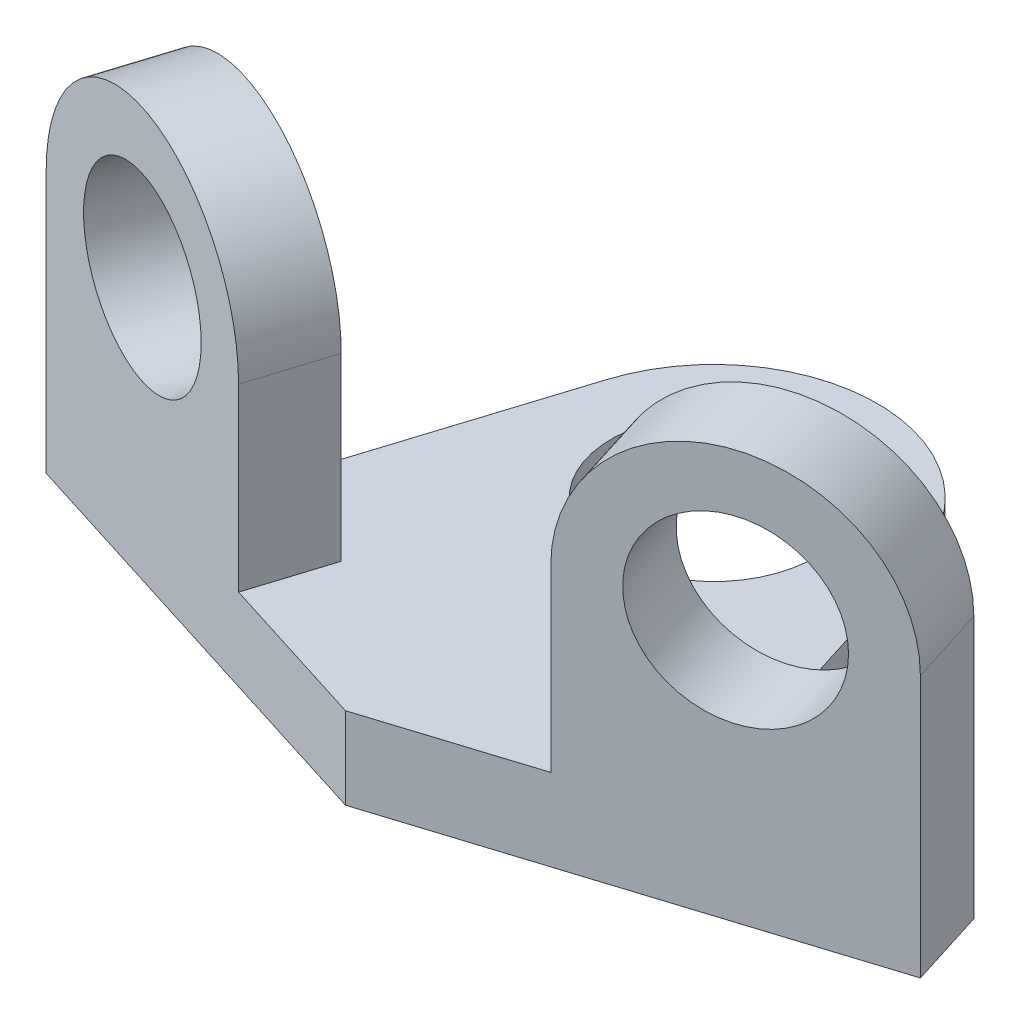
SolidWorks part; units mm, degrees
ref_plane "Front Plane" through (0, 0, 0) normal (0, 0, 1) x (1, 0, 0)
ref_plane "Top Plane" through (0, 0, 0) normal (0, 1, 0) x (1, 0, 0)
ref_plane "Right Plane" through (0, 0, 0) normal (1, 0, 0) x (0, 0, -1)
sketch "Sketch1" plane through (0, 0, 0) normal (0, 1, 0) x (1, 0, 0)
  line L0 (-19.0743, 6.0141) -> (-31.9798, -34.9168)
  line L1 (19.0743, 6.0141) -> (31.9798, -34.9168)
  line L2 (0, 0) -> (0, -45)
  line L3 (0, -45) -> (31.9798, -34.9168)
  line L4 (31.9798, -34.9168) -> (0, -45)
  line L5 (0, -45) -> (-31.9798, -34.9168)
  line L6 (-19.0743, -38.9859) -> (-16.0673, -29.4487)
  line L7 (-16.0673, -29.4487) -> (-50.4011, -18.6233)
  line L8 (-50.4011, -18.6233) -> (-53.4081, -28.1605)
  line L9 (-53.4081, -28.1605) -> (-31.9798, -34.9168)
  line L10 (19.0743, -38.9859) -> (16.0673, -29.4487)
  line L11 (16.0673, -29.4487) -> (50.4011, -18.6233)
  line L12 (50.4011, -18.6233) -> (53.4081, -28.1605)
  line L13 (53.4081, -28.1605) -> (31.9798, -34.9168)
  circle A0 centre (0, 0) radius 12.5
  circle A1 centre (0, 0) radius 20
  dimension "D1" = 25
  dimension "D2" = 40
  dimension "D3" = 45
  dimension "D4" = 17.5
  dimension "D5" = 17.5
  dimension "D6" = 20
  dimension "D7" = 20
  dimension "D8" = 10
  dimension "D9" = 10
  dimension "D10" = 36
  dimension "D11" = 36
extrude "Boss-Extrude1" add sketch "Sketch1" along normal blind 10 contours A1 A0 | A1 L0 L7 L6 L5 L2 | A1 L2 L3 L10 L11 L1 region at (-12.9352, 0, 25.7062) region at (0, 0, -19.4343) region at (12.9352, 0, 25.7062)
extrude "Boss-Extrude2" add sketch "Sketch1<3>" along normal blind 32 contours L8 L9 L0 L7 | L6 L7 L0 L5 | L11 L10 L4 L1 | L13 L12 L11 L1 region at (-24.0235, 0, 32.1828) region at (-41.1905, 0, 26.7701) region at (41.1905, 0, 26.7701) region at (24.0235, 0, 32.1828)
sketch "Sketch1<3>" plane through (0, 0, 0) normal (0, 1, 0) x (1, 0, 0) same geometry as "Sketch1"
sketch "Sketch2" plane through (12.9055, 0, 40.9309) normal (0.3007, 0, 0.9537) x (0.9537, 0, -0.3007)
  line L0 (6.4682, 32) -> (42.4682, 32) construction
  circle A0 centre (24.4682, 32) radius 18
  circle A1 centre (24.4682, 32) radius 11
  line M4 (42.4682, 32) -> (6.4682, 32)
  dimension "D1" = 22
  dimension "D2" = 36
extrude "Boss-Extrude5" add sketch "Sketch2" against normal blind 10 contours A1 A0 M4 | A1 A0 M4 region at (50.0701, 32.4025, 29.2129) region at (36.2412, 14.4025, 33.5732)
sketch "Sketch6" plane through (12.9055, 0, 40.9309) normal (0.3007, 0, 0.9537) x (0.9537, 0, -0.3007)
  line L0 (13.4682, 32) -> (35.4682, 32) construction
  circle A0 centre (24.4682, 32) radius 11
extrude "Cut-Extrude1" cut sketch "Sketch6" against normal blind 10
sketch "Sketch10" plane through (-12.9055, 0, 40.9309) normal (-0.3007, 0, 0.9537) x (0.9537, 0, 0.3007)
  line L0 (-42.4682, 32) -> (-6.4682, 32) construction
  circle A0 centre (-24.4682, 32) radius 18
  circle A1 centre (-24.4682, 32) radius 11
  dimension "D1" = 36
  dimension "D2" = 22
extrude "Boss-Extrude8" add sketch "Sketch10" against normal blind 10
sketch "Sketch11" plane through (-12.9055, 0, 40.9309) normal (-0.3007, 0, 0.9537) x (0.9537, 0, 0.3007)
  line L0 (-35.4682, 32) -> (-13.4682, 32) construction
  circle A0 centre (-24.4682, 32) radius 11
extrude "Cut-Extrude3" cut sketch "Sketch11" against normal blind 10
